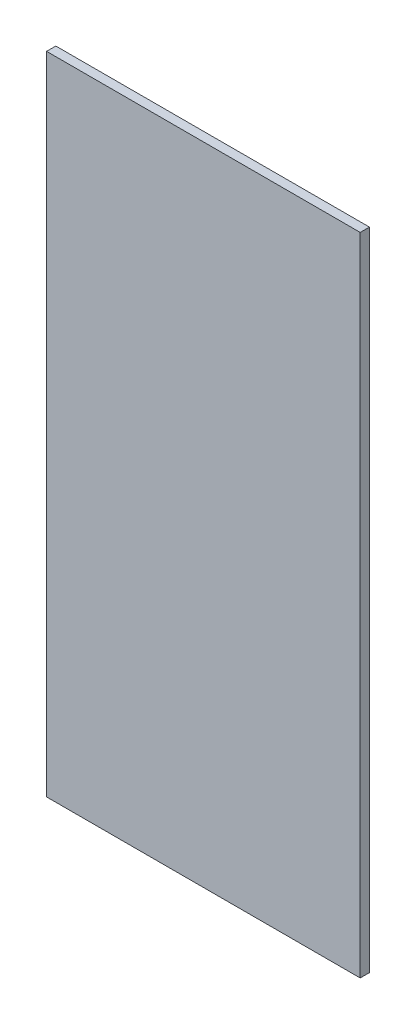
SolidWorks part; units mm, degrees
ref_plane "Front Plane" through (0, 0, 0) normal (0, 0, 1) x (1, 0, 0)
ref_plane "Top Plane" through (0, 0, 0) normal (0, 1, 0) x (1, 0, 0)
ref_plane "Right Plane" through (0, 0, 0) normal (1, 0, 0) x (0, 0, -1)
sketch "Sketch1" plane through (0, 0, 0) normal (0, 0, 1) x (1, 0, 0)
  line L1 (0, 0) -> (-215.9, 0)
  line L2 (0, 0) -> (0, -444.5)
  line L3 (0, -444.5) -> (-215.9, -444.5)
  line L4 (-215.9, 0) -> (-215.9, -444.5)
  dimension "D1" = 215.9
  dimension "D2" = 444.5
extrude "Boss-Extrude1" add sketch "Sketch1" along normal blind 6.35
ref_plane "Plane1" through (0, -444.5, 6.35) normal (1, 0, 0) x (0, 0, -1)
